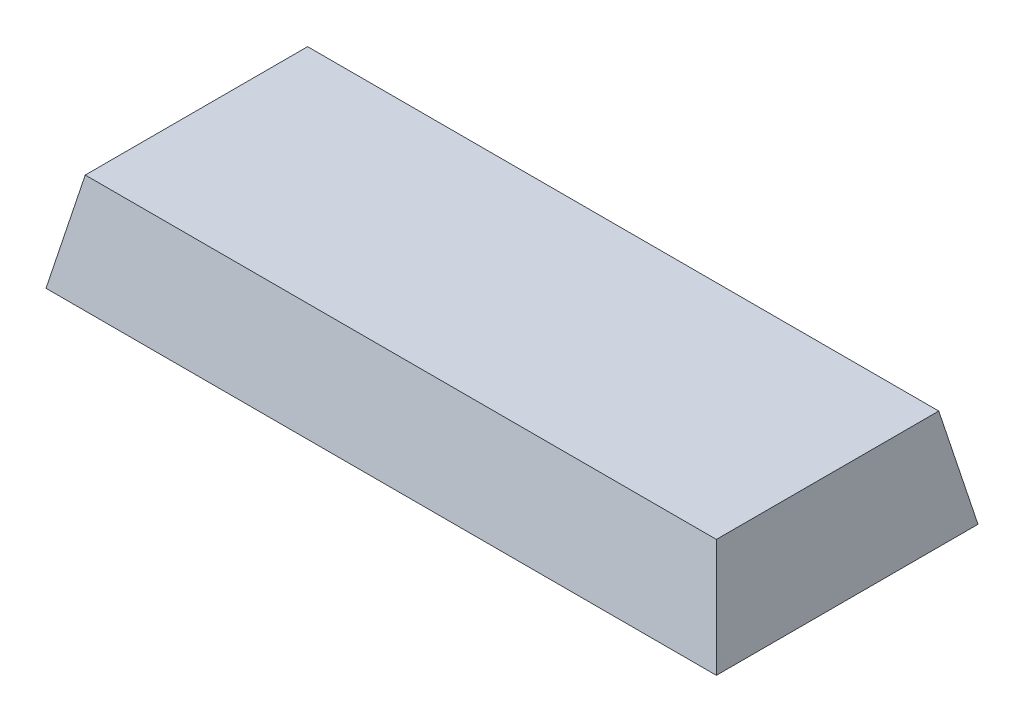
SolidWorks part; units mm, degrees
ref_plane "Front Plane" through (0, 0, 0) normal (0, 0, 1) x (1, 0, 0)
ref_plane "Top Plane" through (0, 0, 0) normal (0, 1, 0) x (1, 0, 0)
ref_plane "Right Plane" through (0, 0, 0) normal (1, 0, 0) x (0, 0, -1)
sketch "Sketch1" plane through (0, 0, 0) normal (0, 1, 0) x (1, 0, 0)
  line L1 (0, 0) -> (20.5, 0)
  line L2 (0, 0) -> (0, 8)
  line L3 (0, 8) -> (20.5, 8)
  line L4 (20.5, 0) -> (20.5, 8)
  dimension "D1" = 8
  dimension "D2" = 20.5
extrude "Boss-Extrude1" add sketch "Sketch1" along normal blind 3
sketch "Sketch2" plane through (0, 0, 0) normal (0, 0, 1) x (1, 0, 0)
  line L0 (0, 0) -> (0.6, 3)
  line L1 (0, 3) -> (20.5, 3) construction
  line L2 (0.6, 3) -> (0, 3)
  line L3 (0, 3) -> (0, 0)
  line L4 (20.5, 0) -> (19.9, 3)
  line L5 (19.9, 3) -> (20.5, 3)
  line L6 (20.5, 3) -> (20.5, 0)
  dimension "D1" = 0.6
  dimension "D2" = 0.6
extrude "Cut-Extrude1" cut sketch "Sketch2" against normal through all both and the other way through all
sketch "Sketch3" plane through (0, 0, 0) normal (1, 0, 0) x (0, 0, -1)
  line L0 (0, 0) -> (0.6, 3)
  line L1 (8, 3) -> (0, 3) construction
  line L2 (0.6, 3) -> (0, 3)
  line L3 (0, 3) -> (0, 0)
  line L4 (8, 3) -> (7.4, 3)
  line L5 (7.4, 3) -> (8, 0)
  line L6 (8, 3) -> (8, 0)
  dimension "D1" = 0.6
  dimension "D2" = 0.6
extrude "Cut-Extrude2" cut sketch "Sketch3" along normal through all both and the other way through all
sketch "Sketch4" plane through (0, 0, 0) normal (0, -1, 0) x (1, 0, 0)
  line L1 (10.25, 0) -> (10.25, -8) construction
  line L2 (20.5, -8) -> (0, -8) construction
  line L3 (0, 0) -> (20.5, 0) construction
  circle A0 centre (10.25, -3.75) radius 1.8
  dimension "D1" = 3.6
  dimension "D2" = 0
  dimension "D3" = 3.75
extrude "Cut-Extrude3" cut sketch "Sketch4" against normal blind 0.8
sketch "Sketch5" plane through (0, 0, 0) normal (0, -1, 0) x (1, 0, 0)
  line L5 (0, 0) -> (20.5, 0) construction
  line L6 (6.25, -8) -> (14.25, -8)
  line L7 (6.25, -8) -> (6.25, -6.9)
  line L8 (6.25, -6.9) -> (14.25, -6.9)
  line L9 (14.25, -8) -> (14.25, -6.9)
  point P2 (10.25, 0)
  dimension "D1" = 1.1
  dimension "D2" = 4
  dimension "D3" = 4
extrude "Boss-Extrude2" add sketch "Sketch5" along normal blind 2
fillet "Fillet1" radius 4 2 edges at (14.25, -2, -7.45) (6.25, -2, -7.45)
